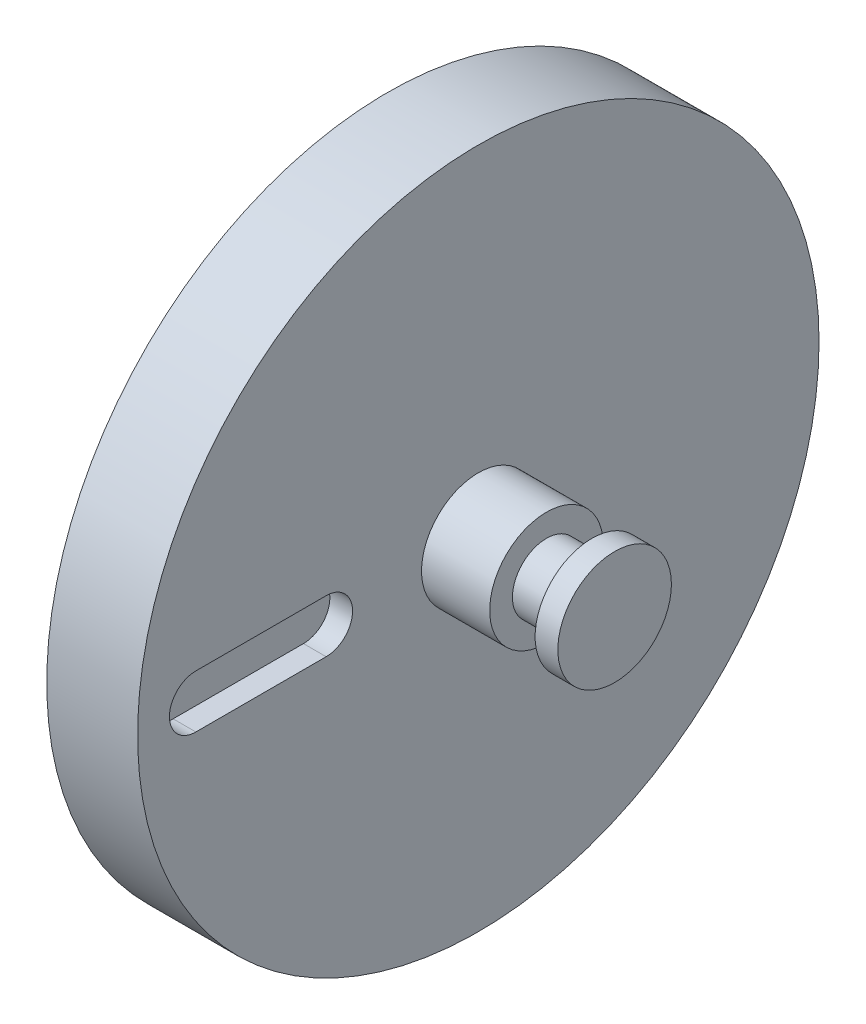
SolidWorks part; units mm, degrees
note: '?' marks a value the reader was unsure of.
ref_plane "前视基准面" through (0, 0, 0) normal (0, 0, 1) x (1, 0, 0)
ref_plane "上视基准面" through (0, 0, 0) normal (0, 1, 0) x (1, 0, 0)
ref_plane "右视基准面" through (0, 0, 0) normal (1, 0, 0) x (0, 0, -1)
other "Configuration Table"
sketch "草图1" plane through (0, 0, 0) normal (1, 0, 0) x (0, 0, -1)
  circle A0 centre (0, 0) radius 75
  dimension "D1" = 150
extrude "凸台-拉伸1" add sketch "草图1" along normal blind 10
sketch "草图2" plane through (10, 0, 0) normal (1, 0, 0) x (0, 0, -1)
  circle A0 centre (0, 0) radius 12.5
  dimension "D1" = 25
extrude "凸台-拉伸2" add sketch "草图2" along normal blind 30
mirror "镜向1" about plane through (0, 0, 0) normal (1, 0, 0) of "凸台-拉伸1", "凸台-拉伸2"
sketch "草图3" plane through (0, 0, 0) normal (0, 1, 0) x (1, 0, 0)
  line L0 (-10, 12.5) -> (-40, 12.5) construction
  line L1 (-35, 12.5) -> (-25, 12.5)
  line L2 (-35, 12.5) -> (-35, 7.5)
  line L3 (-35, 7.5) -> (-25, 7.5)
  line L4 (-25, 12.5) -> (-25, 7.5)
  line L13 (-40, 12.5) -> (-40, -12.5) construction
  dimension "D1" = 5
  dimension "D3" = 10
  dimension "D5" = 5
sketch "草图4" plane through (0, 0, 0) normal (0, 1, 0) x (1, 0, 0)
  line L0 (-40, 0) -> (49960, 0) construction
  line L1 (-40, 12.5) -> (-40, -12.5) construction
  line L2 (40, -12.5) -> (40, 12.5) construction
  point P4 (-40, 0)
  point P7 (40, 0)
sweep "切除-扫描1" cut profiles "草图3" path edge at (-40, 0, -12.5)
mirror "镜向2" about plane through (0, 0, 0) normal (1, 0, 0) of "切除-扫描1"
ref_axis "基准轴1" through (-191.735, 0, 0) along (1, 0, 0)?
sketch "草图5" plane through (-10, 0, 0) normal (-1, 0, 0) x (0, 0, 1)
  line L0 (62.1778, 0) -> (33.4961, 0) construction
  line L1 (62.1778, -5.817) -> (33.4961, -5.817)
  line L2 (62.1778, 5.817) -> (33.4961, 5.817)
  arc A0 (62.1778, -5.817) -> (62.1778, 5.817) centre (62.1778, 0) ccw
  arc A1 (33.4961, 5.817) -> (33.4961, -5.817) centre (33.4961, 0) ccw
  point P4 (47.8369, 0)
extrude "切除-拉伸1" cut sketch "草图5" against normal blind 5
mirror "镜向3" about plane through (0, 0, 0) normal (1, 0, 0) of "切除-拉伸1"
